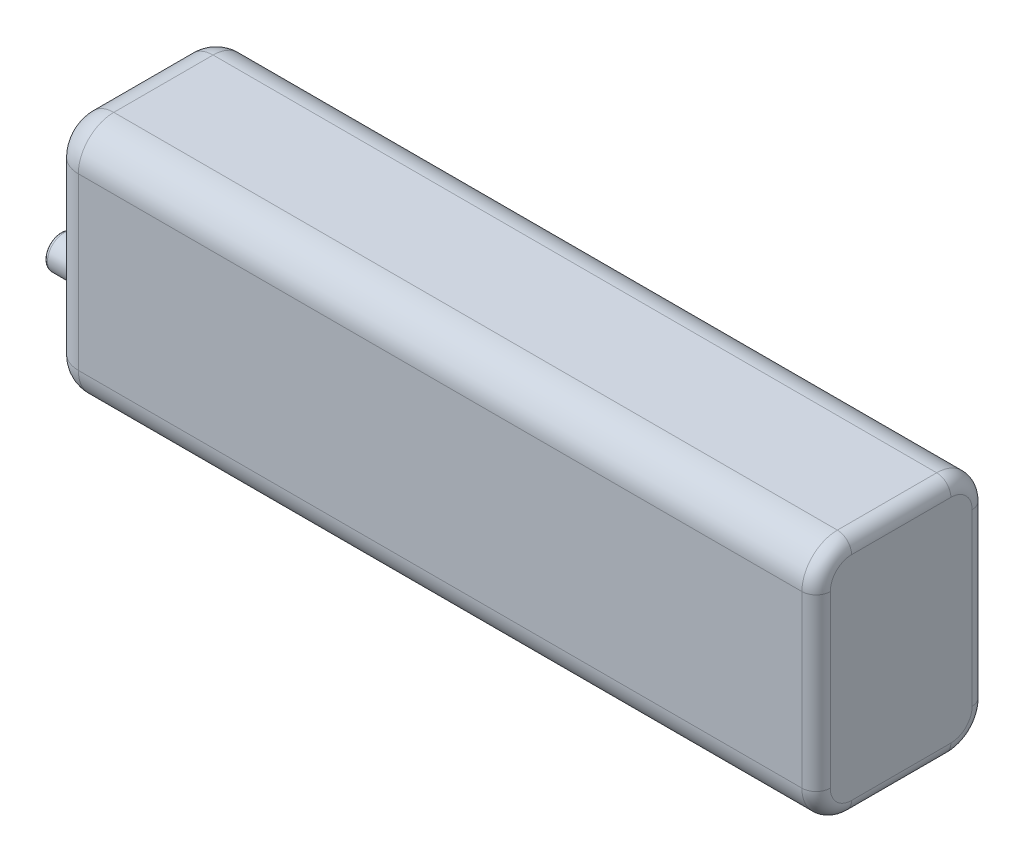
SolidWorks part; units mm, degrees
ref_plane "Front Plane" through (0, 0, 0) normal (0, 0, 1) x (1, 0, 0)
ref_plane "Top Plane" through (0, 0, 0) normal (0, 1, 0) x (1, 0, 0)
ref_plane "Right Plane" through (0, 0, 0) normal (1, 0, 0) x (0, 0, -1)
sketch "Sketch1" plane through (0, 0, 0) normal (0, 0, 1) x (1, 0, 0)
  line L1 (-54, 17) -> (54, 17)
  line L2 (-54, 17) -> (-54, -17)
  line L3 (-54, -17) -> (54, -17)
  line L4 (54, 17) -> (54, -17)
  line L5 (-54, 17) -> (54, -17) construction
  line L6 (-54, -17) -> (54, 17) construction
  point P0 (0, 0)
  dimension "D1" = 108
  dimension "D2" = 34
extrude "Boss-Extrude1" add sketch "Sketch1" along normal blind 24
fillet "Fillet1" radius 5 4 edges at (0, 17, 0) (0, 17, 24) (0, -17, 0) (0, -17, 24)
sketch "Sketch2" plane through (-54, 0, 0) normal (-1, 0, 0) x (0, 0, 1)
  line L1 (17.6229, -3.7162) -> (5.6696, -3.7162)
  line L2 (17.6229, -3.7162) -> (17.6229, -12.0863)
  line L3 (17.6229, -12.0863) -> (5.6696, -12.0863)
  line L4 (5.6696, -3.7162) -> (5.6696, -12.0863)
extrude "Boss-Extrude2" add sketch "Sketch2" along normal blind 3
sketch "Sketch4" plane through (-54, 0, 0) normal (-1, 0, 0) x (0, 0, 1)
  circle A0 centre (14.5181, -8.0315) radius 2.3317
  circle A1 centre (9.0504, -8.0315) radius 2.3317
extrude "Boss-Extrude3" add sketch "Sketch4" along normal blind 8
fillet "Fillet2" radius 0.5 2 edges at (-62, -10.3632, 9.0504) (-62, -10.3632, 14.5181)
chamfer "Chamfer1" distance 1 angle 45 4 edges at (-57, -3.7162, 11.6462) (-57, -7.9013, 5.6696) (-57, -12.0863, 11.6462) (-57, -7.9013, 17.6229)
fillet "Fillet4" radius 4 8 edges at (-54, 15.5355, 22.5355) (-54, 0, 24) (-54, -15.5355, 22.5355) (-54, -17, 12) (-54, -15.5355, 1.4645) (-54, 0, 0) (-54, 15.5355, 1.4645) (-54, 17, 12)
fillet "Fillet5" radius 2 8 edges at (54, -15.5355, 22.5355) (54, -17, 12) (54, -15.5355, 1.4645) (54, 0, 0) (54, 15.5355, 1.4645) (54, 17, 12) (54, 15.5355, 22.5355) (54, 0, 24)
sketch "Sketch7" plane through (0, 0, 24) normal (0, 0, 1) x (1, 0, 0)
  text T0 "           Lithium Polymer Battery \r\n           (11.1 V, 2200 mAh , 25C)" font "Cooper Black" height 3.175
  point P1 (-23.6213, 20.2551)
  point P2 (-44.6163, 0.8269)
  point P3 (-42.5272, 2.4459)
